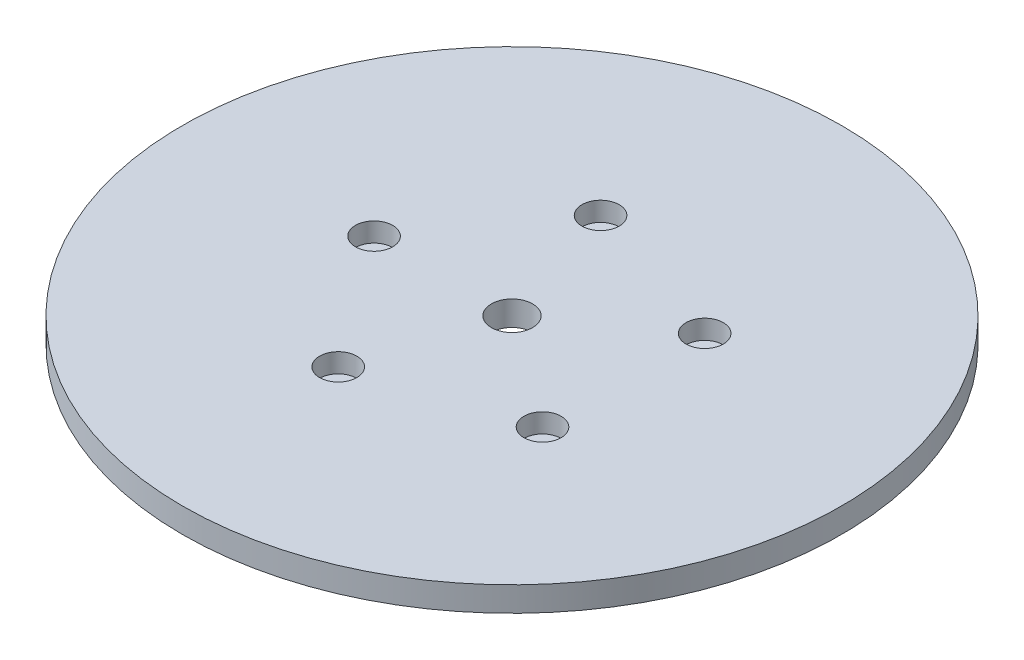
SolidWorks part; units mm, degrees
ref_plane "Front Plane" through (0, 0, 0) normal (0, 0, 1) x (1, 0, 0)
ref_plane "Top Plane" through (0, 0, 0) normal (0, 1, 0) x (1, 0, 0)
ref_plane "Right Plane" through (0, 0, 0) normal (1, 0, 0) x (0, 0, -1)
sketch "Sketch1" plane through (0, 0, 0) normal (0, 1, 0) x (1, 0, 0)
  circle A0 centre (0, 0) radius 80
  dimension "FLANGE_OD" = 160
extrude "Boss-Extrude1" add sketch "Sketch1" along normal blind 6
sketch "Sketch2" plane through (0, 0, 0) normal (0, 1, 0) x (1, 0, 0)
  circle A0 centre (0, 0) radius 5
  dimension "BORE_D" = 10
extrude "Cut-Extrude1" cut sketch "Sketch2" along normal through all
sketch "Sketch3" plane through (0, 6, 0) normal (0, 1, 0) x (1, 0, 0)
  circle A0 centre (0, 0) radius 33.4824 construction
  circle A1 centre (-33.4824, 0) radius 4.5193
  dimension "BOLT_D" = 9.0387
  dimension "BOLT_PCD" = 66.9648
extrude "Cut-Extrude2" cut sketch "Sketch3" against normal blind 4.6732
pattern_circular "CirPattern1" count 5 over 360 about axis through (0, 0, 0) along (0, 1, 0) of "Cut-Extrude2"
